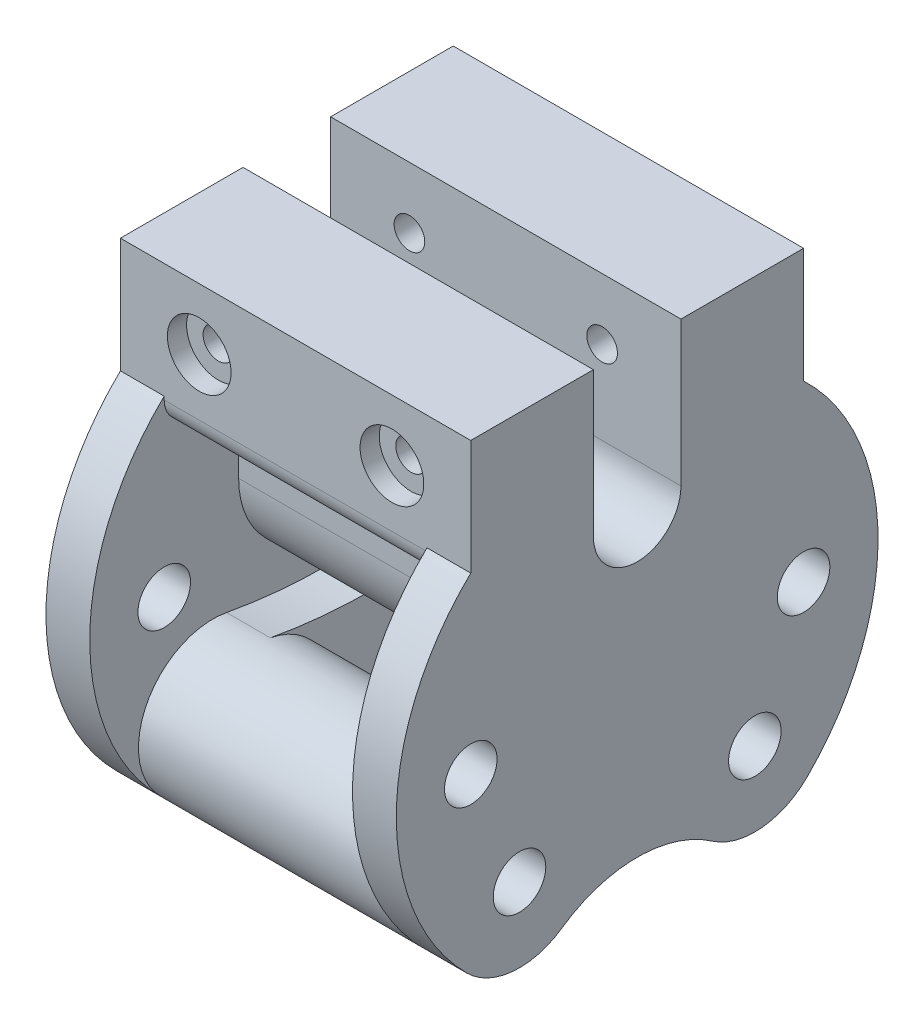
SolidWorks part; units mm, degrees
note: The reader was unsure of these and kept them because the rebuilt part matched: shared geometry of "Sketch4<4>", "Sketch5<2>", "Sketch4<5>".
material "Beryllium Copper, UNS C17000"
ref_plane "Front Plane" through (0, 0, 0) normal (0, 0, 1) x (1, 0, 0)
ref_plane "Top Plane" through (0, 0, 0) normal (0, 1, 0) x (1, 0, 0)
ref_plane "Right Plane" through (0, 0, 0) normal (1, 0, 0) x (0, 0, -1)
sketch "Sketch3" plane through (0, 0, 0) normal (1, 0, 0) x (0, 0, -1)
  line L0 (-38, 6) -> (-38, 33)
  line L1 (-38, 33) -> (-10, 33)
  line L2 (-10, 33) -> (-10, 0)
  line L3 (10, 0) -> (10, 33)
  line L4 (10, 33) -> (38, 33)
  line L5 (38, 33) -> (38, 6)
  line L6 (32, 0) -> (27, 0)
  line L7 (21, -6) -> (21, -18)
  line L8 (-21, -18) -> (-21, -6)
  line L9 (-27, 0) -> (-32, 0)
  line L10 (-10, 33) -> (10, 33) construction
  line L11 (26.8701, -59.8701) -> (0, -33) construction
  line L12 (0, -33) -> (-26.8701, -59.8701) construction
  arc A0 (-10, 0) -> (10, 0) centre (0, 0) ccw
  arc A1 (21, -18) -> (-21, -18) centre (0, -18) cw
  circle A2 centre (-26.8701, -59.8701) radius 17
  circle A4 centre (26.8701, -59.8701) radius 17
  circle A6 centre (0, -33) radius 38 construction
  arc A7 (-21, -6) -> (-27, 0) centre (-27, -6) ccw
  arc A8 (-38, 6) -> (-32, 0) centre (-32, 6) ccw
  arc A9 (27, 0) -> (21, -6) centre (27, -6) ccw
  arc A10 (32, 0) -> (38, 6) centre (32, 6) ccw
  point P9 (0, 33)
  dimension "D1" = 34
  dimension "D3" = 76
  dimension "D7" = 6
  dimension "D8" = 21
  dimension "D9" = 10
  dimension "D10" = 90
  dimension "D2" = 33
  dimension "D4" = 66
  dimension "D5" = 18
  dimension "D6" = 76
extrude "Boss-Extrude1" add sketch "Sketch3" along normal mid plane 60
sketch "Sketch4" plane through (30, 0, 0) normal (1, 0, 0) x (0, 0, -1)
  line L0 (38, 6) -> (38, 33) construction
  line L1 (-38, 33) -> (-38, 6) construction
  line L2 (-26.8701, -59.8701) -> (0, -33) construction
  line L3 (0, -33) -> (0, -68.4317) construction
  line L14 (-10, 33) -> (-38, 33)
  line L15 (-38, 33) -> (-38, 6)
  line L16 (-32, 0) -> (-27, 0)
  line L17 (-21, -6) -> (-21, -18)
  line L18 (21, -18) -> (21, -6)
  line L19 (27, 0) -> (32, 0)
  line L20 (38, 6) -> (38, 33)
  line L21 (38, 33) -> (10, 33)
  line L22 (10, 33) -> (10, 0)
  line L23 (-10, 0) -> (-10, 33)
  line L24 (-10, 33) -> (-38, 33)
  line L25 (-38, 33) -> (-38, 6)
  line L26 (-32, 0) -> (-27, 0)
  line L27 (-21, -6) -> (-21, -18)
  line L28 (21, -18) -> (21, -6)
  line L29 (27, 0) -> (32, 0)
  line L30 (38, 6) -> (38, 33)
  line L31 (38, 33) -> (10, 33)
  line L32 (10, 33) -> (10, 0)
  line L33 (-10, 0) -> (-10, 33)
  arc A1 (-38, 6.7618) -> (-38.8909, -71.8909) centre (0, -33) ccw
  circle A2 centre (-26.8701, -59.8701) radius 17 construction
  arc A3 (38, 6.7618) -> (38.8909, -71.8909) centre (0, -33) cw
  circle A4 centre (26.8701, -59.8701) radius 17 construction
  arc A5 (-17.1511, -73.8179) -> (17.1511, -73.8179) centre (0, -98.4317) cw
  circle A6 centre (0, -33) radius 38 construction
  circle A8 centre (-38, -33) radius 6
  circle A9 centre (-26.8701, -59.8701) radius 6
  circle A11 centre (26.8701, -59.8701) radius 6
  circle A12 centre (-26.8701, -59.8701) radius 17
  circle A13 centre (-26.8701, -59.8701) radius 17
  circle A14 centre (38, -33) radius 6
  arc A15 (-23.7626, -43.1565) -> (23.7626, -43.1565) centre (0, 84.6533) ccw
  circle A16 centre (26.8701, -59.8701) radius 17
  circle A17 centre (26.8701, -59.8701) radius 17
  arc A23 (-38, 6) -> (-32, 0) centre (-32, 6) ccw
  arc A24 (-21, -6) -> (-27, 0) centre (-27, -6) ccw
  arc A25 (-21, -18) -> (21, -18) centre (0, -18) ccw
  arc A26 (27, 0) -> (21, -6) centre (27, -6) ccw
  arc A27 (32, 0) -> (38, 6) centre (32, 6) ccw
  arc A28 (-10, 0) -> (10, 0) centre (0, 0) ccw
  arc A29 (-38, 6) -> (-32, 0) centre (-32, 6) ccw
  arc A30 (-21, -6) -> (-27, 0) centre (-27, -6) ccw
  arc A31 (-21, -18) -> (21, -18) centre (0, -18) ccw
  arc A32 (27, 0) -> (21, -6) centre (27, -6) ccw
  arc A33 (32, 0) -> (38, 6) centre (32, 6) ccw
  arc A34 (-10, 0) -> (10, 0) centre (0, 0) ccw
  point P47 (0, 0)
  line M7 (-10, 33) -> (-38, 33)
  line M8 (-38, 33) -> (-38, 6)
  arc M9 (-38, 6) -> (-32, 0) centre (-32, 6) ccw
  line M10 (-32, 0) -> (-27, 0)
  arc M11 (-27, 0) -> (-21, -6) centre (-27, -6) cw
  line M12 (-21, -6) -> (-21, -18)
  arc M13 (-21, -18) -> (21, -18) centre (0, -18) ccw
  line M14 (21, -18) -> (21, -6)
  arc M15 (21, -6) -> (27, 0) centre (27, -6) cw
  line M16 (27, 0) -> (32, 0)
  arc M17 (32, 0) -> (38, 6) centre (32, 6) ccw
  line M18 (38, 6) -> (38, 33)
  line M19 (38, 33) -> (10, 33)
  line M20 (10, 33) -> (10, 0)
  arc M21 (10, 0) -> (-10, 0) centre (0, 0) cw
  line M22 (-10, 0) -> (-10, 33)
  dimension "D1" = 55
  dimension "D2" = 30
  dimension "D3" = 12
  dimension "D4" = 76
  dimension "D5" = 0
  dimension "D9" = 130
  dimension "D6" = 45
  dimension "D7" = 0
  dimension "D8" = 0
extrude "Boss-Extrude2" add sketch "Sketch4" along normal blind 10 contours A13 L2 L25 A1 A8 M13 M12 M11 M10 M9 | A13 A5 L3 L2 M13 | A17 A3 L3 A5 A14 M18 M17 M16 M15 M14 M13 | L2 L3 L30 L25 M13 M14 M15 M16 M17 M18 M19 M20 M21 M22 M7 M8 M9 M10 M11 M12 | L3 L2 M13 | A13 A9 | A17 A11
extrude "Cut-Extrude1" cut sketch "Sketch4<4>" against normal through all both and the other way through all contours A9 | A11
sketch "Sketch4<4>" plane through (30, 0, 0) normal (1, 0, 0) x (0, 0, -1) same geometry as "Sketch4"
mirror "Mirror1" about plane through (0, 0, 0) normal (1, 0, 0) of "Boss-Extrude2"
sketch "Sketch5" plane through (0, 0, 38) normal (0, 0, -1) x (-1, 0, 0)
  line L0 (-40, 33) -> (40, 33) construction
  line L1 (40, 6.7618) -> (40, 33) construction
  circle A0 centre (-22, 19) radius 3.5
  circle A1 centre (22, 19) radius 3.5
  circle A2 centre (22, 19) radius 7.275
  circle A3 centre (-22, 19) radius 7.275
  point P8 (0, 0)
  point P10 (14.6315, 17.7739)
  point P12 (0, 0)
  dimension "D4" = 7
  dimension "D5" = 14.55
  dimension "D1" = 14
  dimension "D2" = 18
  dimension "D3" = 44
extrude "Cut-Extrude2" cut sketch "Sketch5" along normal blind 4.38
extrude "Cut-Extrude3" cut sketch "Sketch5<2>" against normal through all both and the other way through all contours A1 | A0
sketch "Sketch5<2>" plane through (0, 0, 38) normal (0, 0, -1) x (-1, 0, 0) same geometry as "Sketch5"
extrude "Boss-Extrude3" add sketch "Sketch4<5>" against normal blind 10 contours A17 A15 A13 A5
sketch "Sketch4<5>" plane through (30, 0, 0) normal (1, 0, 0) x (0, 0, -1) same geometry as "Sketch4"
mirror "Mirror2" about plane through (0, 0, 0) normal (1, 0, 0) of "Boss-Extrude3"
